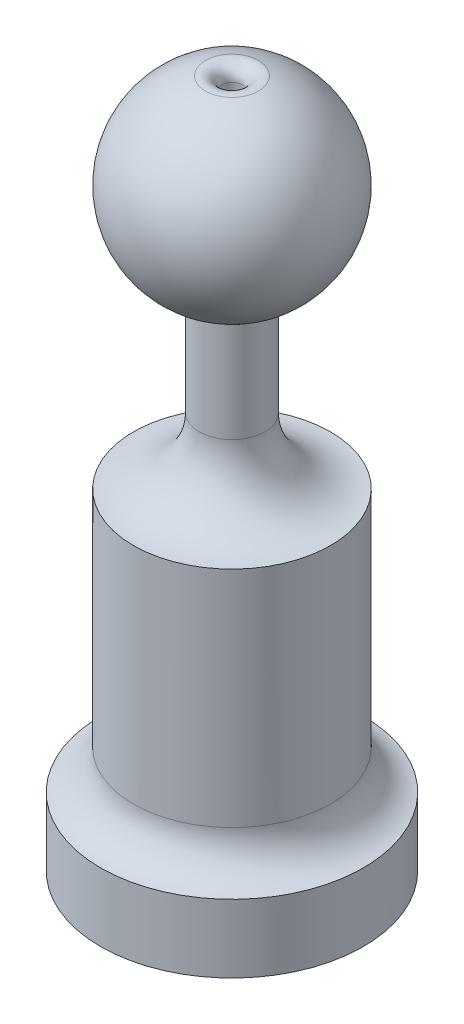
SolidWorks part; units mm, degrees
ref_plane "Front Plane" through (0, 0, 0) normal (0, 0, 1) x (1, 0, 0)
ref_plane "Top Plane" through (0, 0, 0) normal (0, 1, 0) x (1, 0, 0)
ref_plane "Right Plane" through (0, 0, 0) normal (1, 0, 0) x (0, 0, -1)
sketch "Sketch1" plane through (0, 0, 0) normal (0, 0, 1) x (1, 0, 0)
  line L0 (5.2125, 7.3147) -> (-33.7672, 7.3147)
  line L1 (-19.3266, -0.5859) -> (-9.2281, -0.5859)
  line L2 (-33.7672, 7.3147) -> (-19.3266, -0.5859)
  line L3 (5.2125, 7.3147) -> (-9.2281, -0.5859)
  line L4 (-14.2773, 7.3147) -> (-14.2773, -0.5859)
  line L5 (-4.2773, 7.3147) -> (-4.2773, 2.1227)
  line L6 (-9.2173, 7.3147) -> (-9.2173, -0.5801)
  line L7 (-9.2173, 5.4141) -> (-14.2773, 5.4141)
  dimension "D1" = 10
  dimension "D2" = 5.06
  dimension "D3" = 6
revolve "Revolve1" add sketch "Sketch1" angle 360 about L4 region at (-6.9174, 3.9965, 0) region at (-11.7473, 6.3644, 0)
fillet "Fillet1" radius 1 1 edges at (-14.2773, -0.5801, 5.06)
sketch "Sketch2" plane through (0, 7.3147, 0) normal (0, 1, 0) x (1, 0, 0)
  circle A0 centre (-14.2773, 0) radius 7.5
  dimension "D2" = 15
extrude "Boss-Extrude1" add sketch "Sketch2" along normal blind 20
sketch "Sketch3" plane through (0, 5.4141, 0) normal (0, -1, 0) x (1, 0, 0)
  circle A1 centre (-14.2773, 0) radius 5.06
  circle A2 centre (-14.2773, 0) radius 5.06
  dimension "D1" = 0
extrude "Cut-Extrude1" cut sketch "Sketch3" against normal blind 5
sketch "Sketch4" plane through (0, 27.3147, 0) normal (0, 1, 0) x (1, 0, 0)
  circle A0 centre (-14.2773, 0) radius 2.5
  dimension "D1" = 5
extrude "Boss-Extrude2" add sketch "Sketch4" along normal blind 20
sketch "Sketch5" plane through (0, 47.3147, 0) normal (0, 1, 0) x (1, 0, 0)
  line L0 (-21.7773, 0) -> (-6.7773, 0)
  circle A0 centre (-14.2773, 0) radius 7.5
  circle A1 centre (-14.2773, 0) radius 2.5
  circle A2 centre (-14.2773, 0) radius 2.5
  dimension "D2" = 15
  dimension "D1" = 0
revolve "Revolve2" add sketch "Sketch5" angle 360 about L0 region at (-14.2773, 47.3147, -3.4484) region at (-14.2773, 47.3147, -1.061)
fillet "Fillet2" radius 5 1 edges at (-14.2773, 27.3147, 2.5)
sketch "Sketch6" plane through (0, 10.4141, 0) normal (0, -1, 0) x (1, 0, 0)
  circle A0 centre (-14.2773, 0) radius 0.75
  dimension "D1" = 1.5
extrude "Cut-Extrude2" cut sketch "Sketch6" against normal blind 45
fillet "Fillet3" radius 1 1 edges at (-14.2773, 54.7771, -0.75)
fillet "Fillet4" radius 3 1 edges at (-14.2773, 7.3147, 7.5)
